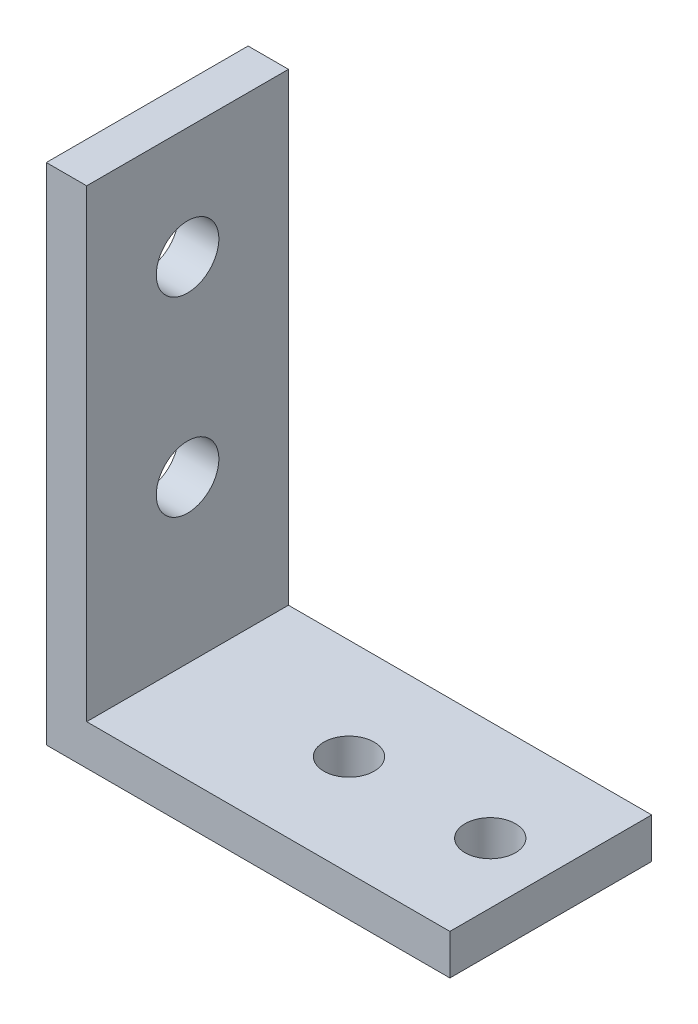
SolidWorks part; units mm, degrees
material "1060 Alloy"
ref_plane "Front Plane" through (0, 0, 0) normal (0, 0, 1) x (1, 0, 0)
ref_plane "Top Plane" through (0, 0, 0) normal (0, 1, 0) x (1, 0, 0)
ref_plane "Right Plane" through (0, 0, 0) normal (1, 0, 0) x (0, 0, -1)
sketch "Sketch1" plane through (0, 0, 0) normal (0, 0, 1) x (1, 0, 0)
  line L0 (0, 0) -> (0, 25)
  line L1 (0, 25) -> (2, 25)
  line L2 (2, 25) -> (2, 2)
  line L3 (2, 2) -> (20, 2)
  line L4 (20, 2) -> (20, 0)
  line L5 (20, 0) -> (0, 0)
  dimension "D1" = 2
  dimension "D2" = 25
  dimension "D3" = 20
extrude "Base" add sketch "Sketch1" along normal mid plane 10
hole_wizard "M3x0.5 MountHoles" positions "Sketch3" profile "Sketch4" tap size "M3x0.5" standard "ANSI Metric" end condition through all
sketch "Sketch3" plane through (0, 0, 0) normal (0, -1, 0) x (-1, 0, 0)
  line L1 (0, -5) -> (0, 5) construction
  point P0 (-10, 0)
  point P2 (-17, 0)
  dimension "D1" = 10
  dimension "D2" = 17
cosmetic thread "Hole Thread3" parameters "D2"=3
cosmetic thread "Hole Thread4" parameters "D2"=3
sketch "Sketch4" plane through (10, 0, 0) normal (1, 0, 0) x (0, 0, -1)
  line L0 (0, 0) -> (0, 25)
  line L1 (0, 25) -> (1.25, 25)
  line L2 (1.25, 25) -> (1.25, 0)
  line L5 (1.25, 0) -> (0, 0)
  line L11 (0, -6.35) -> (0, 107.95) construction
  dimension "Thru Tap Drill Dia." = 2.5
  dimension "Thru Tap Drill Depth" = 25
hole_wizard "Ø3.1 (3.1) LimitSwitchHoles" positions "3DSketch1" profile "Sketch5" hole size "Ø3.1" standard "ANSI Metric" end condition through all
sketch3d "3DSketch1"
  line L1 (0, 0, 5) -> (0, 0, -5) construction
  point P16 (0, 10, 0)
  point P18 (0, 19.45, 0)
  point P23 (0, 0, 0)
  point P24 (0, 0, 0)
  point P25 (0, 0, 0)
  point P29 (0, 0, 0)
  point P30 (0, 0, 0)
  point P31 (0, 0, 0)
  dimension "D1" = 10
  dimension "D2" = 19.45
sketch "Sketch5" plane through (0, 10, 0) normal (0, 1, 0) x (0, 0, 1)
  line L0 (0, 0) -> (0, 20)
  line L1 (0, 20) -> (1.55, 20)
  line L2 (1.55, 20) -> (1.55, 0)
  line L5 (1.55, 0) -> (0, 0)
  line L11 (0, -6.35) -> (0, 107.95) construction
  dimension "Thru Hole Dia." = 3.1
  dimension "Thru Hole Depth" = 20
